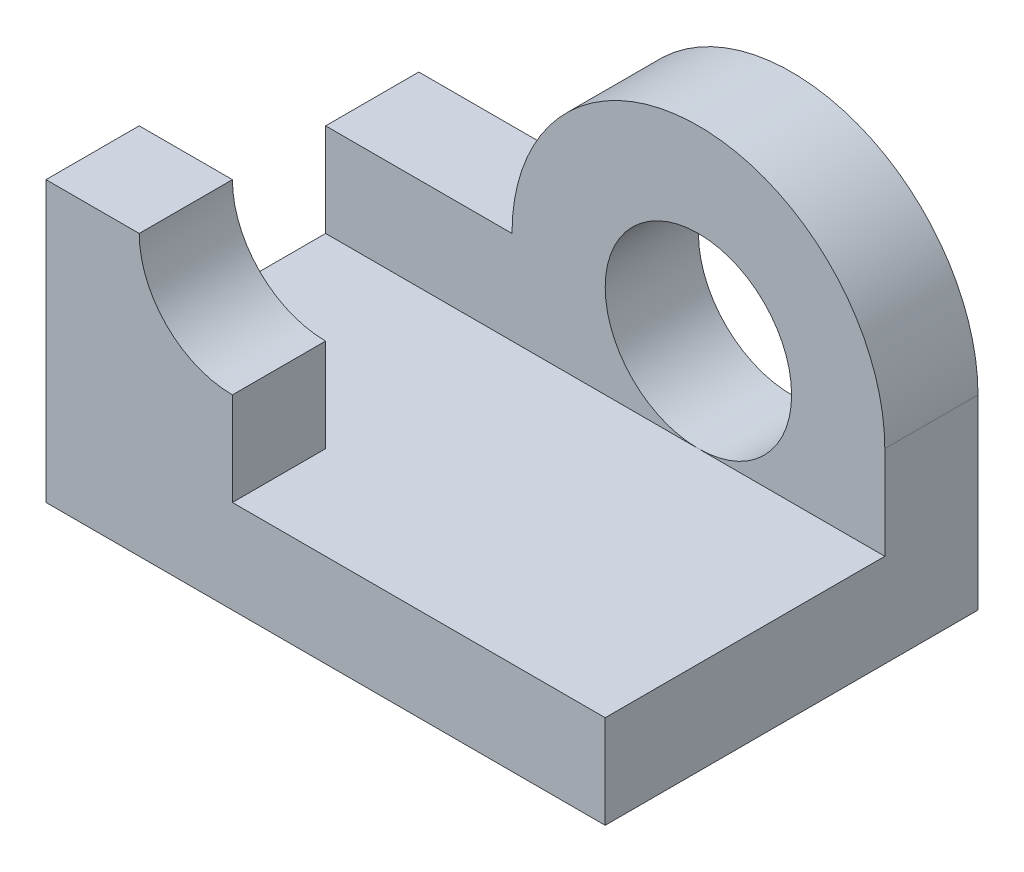
SolidWorks part; units mm, degrees
ref_plane "前基準面" through (0, 0, 0) normal (0, 0, 1) x (1, 0, 0)
ref_plane "上基準面" through (0, 0, 0) normal (0, 1, 0) x (1, 0, 0)
ref_plane "右基準面" through (0, 0, 0) normal (1, 0, 0) x (0, 0, -1)
sketch "草圖1" plane through (0, 0, 0) normal (0, 1, 0) x (1, 0, 0)
  line L1 (0, 0) -> (60, 0)
  line L2 (0, 0) -> (0, 40)
  line L3 (0, 40) -> (60, 40)
  line L4 (60, 0) -> (60, 40)
  dimension "D1" = 40
  dimension "D2" = 60
extrude "填料-伸長1" add sketch "草圖1" against normal blind 10
sketch "草圖2" plane through (0, 0, 0) normal (0, 0, 1) x (1, 0, 0)
  line L0 (0, 0) -> (0, 20)
  line L1 (0, 20) -> (10, 20)
  line L2 (20, 10) -> (20, 0)
  line L3 (0, 0) -> (60, 0) construction
  line L4 (20, 0) -> (0, 0)
  arc A0 (10, 20) -> (20, 10) centre (20, 20) ccw
  dimension "D4" = 10
  dimension "D1" = 20
  dimension "D2" = 10
  dimension "D3" = 20
extrude "填料-伸長2" add sketch "草圖2" against normal blind 10
sketch "草圖3" plane through (0, 0, -40) normal (0, 0, -1) x (-1, 0, 0)
  line L0 (-60, 0) -> (-60, 10)
  line L1 (-60, 10) -> (-50, 10)
  line L2 (-20, 0) -> (-20, 10) construction
  line L3 (-20, 10) -> (-20, 0)
  line L4 (-30, 10) -> (-20, 10)
  line L5 (-20, 10) -> (0, 10)
  line L6 (0, 20) -> (0, 0) construction
  line L7 (0, 10) -> (0, 0)
  line L8 (0, 0) -> (-20, 0)
  circle A0 centre (-40, 10) radius 10
  arc A1 (-20, 10) -> (-60, 10) centre (-40, 10) ccw
  line M2 (0, 0) -> (-60, 0)
  dimension "D2" = 20
extrude "填料-伸長6" add sketch "草圖3" against normal blind 10 contours L7 L5 L3 M2 region at (10, 5, -40)
extrude "填料-伸長7" add sketch "草圖3<5>" against normal blind 10 contours A0 L3 L4 M2 | A0 L1 L0 M2 region at (53.7219, 4.5112, -40) region at (26.2781, 4.5112, -40)
sketch "草圖3<5>" plane through (0, 0, -40) normal (0, 0, -1) x (-1, 0, 0) same geometry as "草圖3"
extrude "填料-伸長8" add sketch "草圖3<6>" against normal blind 10 contours L4 A1 L1 A0 region at (40, 29.5528, -40)
sketch "草圖3<6>" plane through (0, 0, -40) normal (0, 0, -1) x (-1, 0, 0) same geometry as "草圖3"
